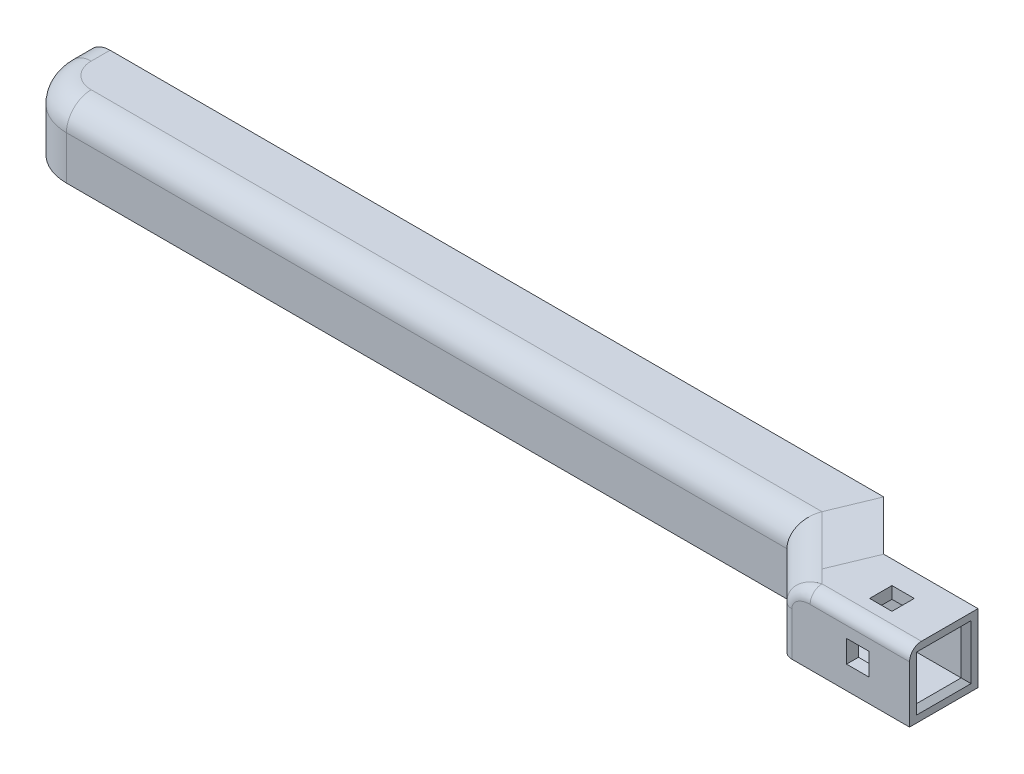
SolidWorks part; units mm, degrees
ref_plane "Front Plane" through (0, 0, 0) normal (0, 0, 1) x (1, 0, 0)
ref_plane "Top Plane" through (0, 0, 0) normal (0, 1, 0) x (1, 0, 0)
ref_plane "Right Plane" through (0, 0, 0) normal (1, 0, 0) x (0, 0, -1)
sketch "Sketch1" plane through (0, 0, 0) normal (1, 0, 0) x (0, 0, -1)
  line L0 (-2.4, 11.4) -> (11.4, 11.4)
  line L1 (0, 0) -> (9, 0)
  line L2 (0, 0) -> (0, 9)
  line L3 (0, 9) -> (9, 9)
  line L4 (9, 0) -> (9, 9)
  line L5 (11.4, -2.4) -> (11.4, 11.4)
  line L6 (-2.4, -2.4) -> (11.4, -2.4)
  line L7 (-2.4, -2.4) -> (-2.4, 11.4)
  dimension "D1" = 9
  dimension "D2" = 2.4
sketch "Sketch2" plane through (0, 0, 0) normal (0, 1, 0) x (1, 0, 0)
  line L1 (0, 9) -> (-20, 9)
  line L2 (-20, 9) -> (-20, 19) construction
  line L3 (-20, 19) -> (-30, 19) construction
  line L4 (-20, 9) -> (-30, 19)
  line L5 (-30, 19) -> (-190, 19)
  dimension "D2" = 10
  dimension "D3" = 160
  dimension "D4" = 20
sweep "Sweep1" add profiles "Sketch1" path "Sketch2"
sketch "Sketch6" plane through (-190, 0, 0) normal (-1, 0, 0) x (0, 0, 1)
  line L1 (-10, 9) -> (-19, 9)
  line L2 (-10, 9) -> (-10, 0)
  line L3 (-10, 0) -> (-19, 0)
  line L4 (-19, 9) -> (-19, 0)
extrude "Boss-Extrude1" add sketch "Sketch6" against normal up to next
fillet "Fillet1" radius 10 1 edges at (-190, 4.5, -7.6)
fillet "Fillet2" radius 5 4 edges at (-190, 11.4, -19.5) (-187.0711, 11.4, -10.5289) (-29.722, 11.4, -2.6) (-107.361, 11.4, -7.6)
fillet "Fillet3" radius 2.4 3 edges at (-8.8255, 11.4, 2.4) (-22.651, 9.9355, 2.4) (-24.722, 2, 2.4)
sketch "Sketch7" plane through (0, 0, -9) normal (0, 0, 1) x (1, 0, 0)
  line L1 (-8.2, 6.75) -> (-12.7, 6.75)
  line L2 (-8.2, 6.75) -> (-8.2, 2.25)
  line L3 (-8.2, 2.25) -> (-12.7, 2.25)
  line L4 (-12.7, 6.75) -> (-12.7, 2.25)
  line L5 (-10.45, 6.75) -> (-10.45, 9) construction
  line L7 (-10.45, 2.25) -> (-10.45, 0) construction
  line L9 (0, 9) -> (-20, 9) construction
  line L10 (0, 0) -> (-20, 0) construction
  line L11 (0, 9) -> (0, 0) construction
  dimension "D1" = 4.5
  dimension "D2" = 8.2
extrude "Cut-Extrude1" cut sketch "Sketch7" against normal up to next contours L2 L1 L4 L3
chamfer "Chamfer1" distance 1 angle 45 4 edges at (0, 4.5, -9) (0, 9, -4.5) (0, 4.5, 0) (0, 0, -4.5)
ref_plane "Plane1" through (-1, 0, 0) normal (0, 0, -1) x (-1, 0, 0)
sketch "Sketch8" plane through (-1, 0, 0) normal (0, 0, -1) x (-1, 0, 0)
  line L0 (0, 9) -> (22.7279, 9) construction
  line L1 (11.7, 6.75) -> (7.2, 6.75)
  line L2 (11.7, 6.75) -> (11.7, 2.25)
  line L3 (11.7, 2.25) -> (7.2, 2.25)
  line L4 (7.2, 6.75) -> (7.2, 2.25)
  line L5 (9.45, 6.75) -> (9.45, 9) construction
  line L6 (0, 0) -> (22.7279, 0) construction
  line L7 (9.45, 2.25) -> (9.45, 0) construction
  line L8 (-1, 9) -> (-1, -2.4) construction
  point P4 (0, 0)
  point P9 (0, 0)
  dimension "D1" = 4.5
  dimension "D2" = 8.2
sketch "Sketch9" plane through (0, 0, 0) normal (0, 1, 0) x (1, 0, 0)
  line L0 (-1, 9) -> (-20, 9) construction
  line L1 (-8.2, 6.75) -> (-12.7, 6.75)
  line L2 (-8.2, 6.75) -> (-8.2, 2.25)
  line L3 (-8.2, 2.25) -> (-12.7, 2.25)
  line L4 (-12.7, 6.75) -> (-12.7, 2.25)
  line L5 (-10.45, 6.75) -> (-10.45, 9) construction
  line L6 (-1, 0) -> (-23.7279, 0) construction
  line L7 (-10.45, 2.25) -> (-10.45, 0) construction
  line L8 (0, 10) -> (0, -1) construction
  point P4 (0, 0)
  point P9 (0, 0)
  point P10 (0, 0)
  point P15 (-8.0078, 0)
  dimension "D1" = 4.5
  dimension "D2" = 8.2
sketch "Sketch10" plane through (0, 9, 0) normal (0, -1, 0) x (-1, 0, 0)
  line L0 (1, 0) -> (23.7279, 0) construction
  line L1 (12.7, 6.75) -> (8.2, 6.75)
  line L2 (12.7, 6.75) -> (12.7, 2.25)
  line L3 (12.7, 2.25) -> (8.2, 2.25)
  line L4 (8.2, 6.75) -> (8.2, 2.25)
  line L5 (10.45, 6.75) -> (10.45, 9) construction
  line L6 (1, 9) -> (20, 9) construction
  line L7 (10.45, 2.25) -> (10.45, 0) construction
  line L8 (0, -1) -> (0, 10) construction
  point P4 (0, 0)
  point P9 (0, 0)
  dimension "D1" = 4.5
  dimension "D2" = 8.2
extrude "Cut-Extrude2" cut sketch "Sketch8" against normal up to next
extrude "Cut-Extrude3" cut sketch "Sketch10" against normal up to next
extrude "Cut-Extrude4" cut sketch "Sketch9" against normal up to next
equation "\"Tube_ID\"= 9"
equation "\"D1@Sketch1\"=\"Tube_ID\""
equation "\"wall_Thickness\"=2.4"
equation "\"D2@Sketch1\"=\"wall_Thickness\""
equation "\"Extension_Length\"= 160"
equation "\"D3@Sketch2\"=\"Extension_Length\""
equation "\"Offset_Amount\"=10"
equation "\"D2@Sketch2\"=\"Offset_Amount\""
equation "\"Socket_Depth\"=20"
equation "\"D4@Sketch2\"=\"Socket_Depth\""
equation "\"Overall_Length\"= \"Extension_Length\" + \"Offset_Amount\" + \"Socket_Depth\""
equation "\"hole_from_edge\"=8.2"
equation "\"D2@Sketch7\"=\"hole_from_edge\""
equation "\"D2@Sketch8\"=\"hole_from_edge\""
equation "\"D2@Sketch9\"=\"hole_from_edge\""
equation "\"D2@Sketch10\"=\"hole_from_edge\""
